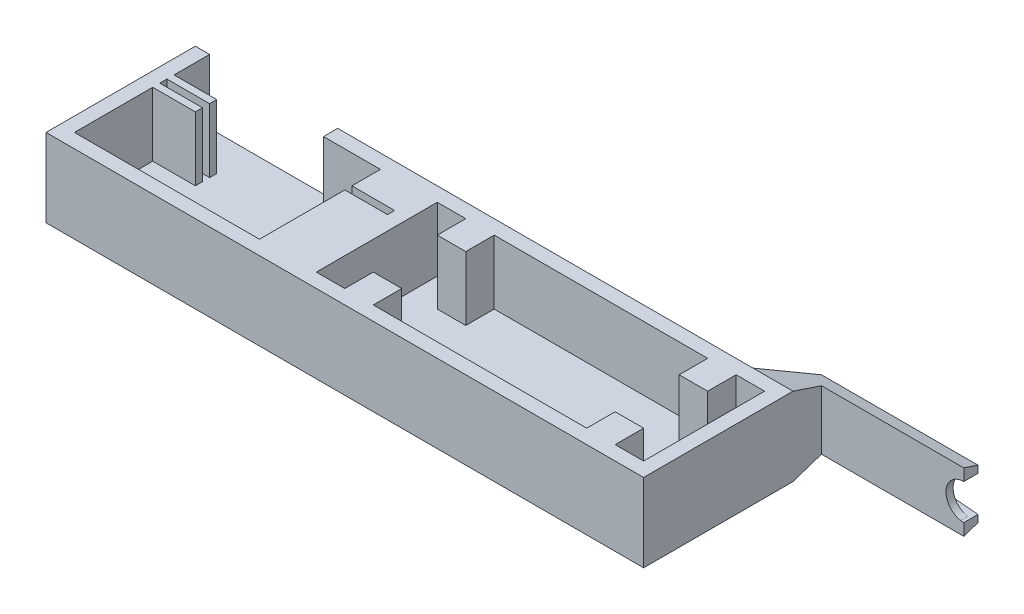
SolidWorks part; units mm, degrees
ref_plane "Front Plane" through (0, 0, 0) normal (0, 0, 1) x (1, 0, 0)
ref_plane "Top Plane" through (0, 0, 0) normal (0, 1, 0) x (1, 0, 0)
ref_plane "Right Plane" through (0, 0, 0) normal (1, 0, 0) x (0, 0, -1)
sketch "Sketch1" plane through (0, 0, 0) normal (0, 1, 0) x (1, 0, 0)
  line L0 (0, 0) -> (40, 0) construction
  line L1 (0, 0) -> (-40, 0) construction
  line L2 (40, -8.5) -> (40, 8.5)
  line L3 (40, 8.5) -> (-40, 8.5)
  line L4 (-40, 8.5) -> (-40, -8.5)
  line L5 (-40, -8.5) -> (40, -8.5)
  line L6 (40, 8.5) -> (40, 10.5) construction
  line L7 (40, 10.5) -> (42, 10.5) construction
  line L8 (-40, -8.5) -> (-40, -10.5) construction
  line L9 (-40, -10.5) -> (-42, -10.5) construction
  line L10 (-40, 0) -> (-34, 0) construction
  line L11 (-42, -10.5) -> (42, -10.5)
  line L12 (-42, -10.5) -> (-42, 10.5)
  line L13 (-42, 10.5) -> (42, 10.5)
  line L14 (42, -10.5) -> (42, 10.5)
  line L15 (-34, 0) -> (-14, 0) construction
  line L16 (-34, -8.5) -> (-34, 3.5)
  line L17 (-34, 3.5) -> (-40, 3.5)
  line L18 (-40, 3.5) -> (-40, 4.4487)
  line L19 (-34, 4.5) -> (-40, 4.5)
  line L20 (-34, 4.5) -> (-34, 8.5)
  line L21 (-14, 3.5) -> (-14, -8.5)
  line L22 (-14, 3.5) -> (-8, 3.5)
  line L23 (-8, 3.5) -> (-8, 4.5)
  line L24 (-8, 4.5) -> (-14, 4.5)
  line L25 (-14, 4.5) -> (-14, 8.5)
  line L26 (-8, 3.5) -> (-6, 3.5) construction
  line L27 (-6, 8.5) -> (-6, -8.5)
  line L28 (62, 14.5) -> (42, 14.5)
  line L29 (42, 14.5) -> (42, 10.5)
  line L30 (62, 16.5) -> (40, 16.5)
  line L31 (40, 16.5) -> (36.3801, 10.5)
  line L32 (62, 14.5) -> (62, 16.5)
  line L33 (40, 10.5) -> (36.3801, 10.5) construction
  point P7 (40, 0)
extrude "Boss-Extrude1" add sketch "Sketch1" along normal blind 2 contours L31 L13 L29 L28 L32 L30 | L3 L27 L5 L2 | L27 L3 L25 L24 L23 L22 L21 L5 | L19 L20 L3 L4 | L24 L25 L3 L20 L19 L4 L17 L16 L5 L21 L22 L23 | L16 L17 L4 L5 | L11 L14 L13 L12 L5 L4 L3 L2 region at (17, 0, 0) region at (-9.9538, 0, 0.1846) region at (-24, 0, -0.1364) region at (-37, 0, 2.5) region at (-37, 0, -6.5) region at (-41.1341, 0, 0) region at (47.6185, 0, -14.5999)
extrude "Boss-Extrude2" add sketch "Sketch1<4>" along normal blind 11 contours L31 L13 L29 L28 L32 L30 | L11 L14 L13 L12 L5 L4 L3 L2 | L27 L3 L25 L24 L23 L22 L21 L5 | L16 L17 L4 L5 | L19 L20 L3 L4 region at (-9.9538, 0, 0.1846) region at (-37, 0, 2.5) region at (-37, 0, -6.5) region at (-41.1341, 0, 0) region at (47.6185, 0, -14.5999)
sketch "Sketch1<4>" plane through (0, 0, 0) normal (0, 1, 0) x (1, 0, 0) same geometry as "Sketch1"
sketch "Sketch2" plane through (0, 11, 0) normal (0, 1, 0) x (1, 0, 0)
  line L1 (-40, 5.5) -> (-34, 5.5)
  line L2 (-34, 4.5) -> (-34, 8.5) construction
  line L3 (-34, 5.5) -> (-34, 8.5)
  line L4 (-34, 8.5) -> (-40, 8.5)
  line L5 (-40, 8.5) -> (-40, 5.5)
  line L6 (-40, 2.5) -> (-34, 2.5)
  line L7 (-34, -8.5) -> (-34, 3.5) construction
  line L8 (-34, 2.5) -> (-34, -8.5)
  line L9 (-34, -8.5) -> (-40, -8.5)
  line L10 (-40, -8.5) -> (-40, 2.5)
extrude "Cut-Extrude1" cut sketch "Sketch2" against normal blind 9
sketch "Sketch3" plane through (0, 0, -10.5) normal (0, 0, -1) x (-1, 0, 0)
  line L0 (42, 9) -> (40, 9) construction
  line L1 (42, 11) -> (42, 0) construction
  line L2 (40, 2) -> (22, 2)
  line L4 (40, 0) -> (40, 2) construction
  line L5 (42, 0) -> (-36.3801, 0) construction
  line L6 (22, 2) -> (22, 11)
  line L7 (42, 11) -> (-36.3801, 11) construction
  line L8 (22, 11) -> (40, 11)
  line L9 (40, 11) -> (40, 2)
extrude "Cut-Extrude2" cut sketch "Sketch3" against normal blind 2
sketch "Sketch4" plane through (0, 2, 0) normal (0, 1, 0) x (1, 0, 0)
  line L0 (-6, 8.5) -> (-2, 8.5) construction
  line L1 (40, 8.5) -> (-6, 8.5) construction
  line L2 (-2, 8.5) -> (-2, 4.5)
  line L3 (-2, 4.5) -> (2, 4.5)
  line L4 (2, 4.5) -> (2, 8.5)
  line L5 (-6, 8.5) -> (40, 8.5) construction
  line L6 (2, 8.5) -> (-2, 8.5)
  line L7 (-2, -8.5) -> (-2, -4.5)
  line L8 (40, -8.5) -> (-6, -8.5) construction
  line L9 (-2, -4.5) -> (2, -4.5)
  line L10 (2, -4.5) -> (2, -8.5)
  line L11 (-6, -8.5) -> (40, -8.5) construction
  line L12 (2, -8.5) -> (-2, -8.5)
  line L13 (40, 8.5) -> (36, 8.5) construction
  line L14 (36, 8.5) -> (36, 4.5)
  line L15 (36, 4.5) -> (32, 4.5)
  line L16 (32, 4.5) -> (32, 8.5)
  line L17 (32, 8.5) -> (36, 8.5)
  line L18 (36, -8.5) -> (36, -4.5)
  line L19 (36, -4.5) -> (32, -4.5)
  line L20 (32, -4.5) -> (32, -8.5)
  line L21 (32, -8.5) -> (36, -8.5)
extrude "Boss-Extrude3" add sketch "Sketch4" along normal blind 9 contours L6 L2 L3 L4 | L12 L7 L9 L10 | L21 L18 L19 L20 | L17 L14 L15 L16
sketch "Sketch6" plane through (0, 0, -16.5) normal (0, 0, -1) x (-1, 0, 0)
  line L0 (-62, 11) -> (-62, 5.5) construction
  line L1 (-62, 5.5) -> (-55.5, 5.5) construction
  line L2 (-62, 11) -> (-62, 0) construction
  line L3 (-62, 5.5) -> (-50.5, 5.5) construction
  line L4 (-62, 3) -> (-50.5, 4)
  line L5 (-50.5, 7) -> (-62, 8)
  line L6 (-50.5, 5.5) -> (-53, 5.5) construction
  circle A0 centre (-50.5, 5.5) radius 0.5
  circle A1 centre (-50.5, 5.5) radius 1.5
  circle A2 centre (-62, 5.5) radius 2.5
  circle A3 centre (-53, 5.5) radius 0.5
  circle A4 centre (-55.5, 5.5) radius 0.5
  line M5 (-62, 11) -> (-62, 0)
extrude "Cut-Extrude3" cut sketch "Sketch6" against normal blind 1 contours A2 L4 A1 L5 A4 A3 | A1 A0 region at (56.1616, 5.5, -16.5) region at (51.9576, 5.5, -16.5)
extrude "Cut-Extrude4" cut sketch "Sketch6<3>" against normal blind 2 contours L4 A2 L5 M5 region at (60.9385, 5.5, -16.5)
sketch "Sketch6<3>" plane through (0, 0, -16.5) normal (0, 0, -1) x (-1, 0, 0) same geometry as "Sketch6"
sketch "Sketch7" plane through (42, 0, 0) normal (1, 0, 0) x (0, 0, -1)
  line L0 (-10.5, 11) -> (10.5, 11) construction
  line L1 (14.5, 11) -> (-10.5, 11) construction
  line L2 (16.5, 8) -> (16.5, 9) construction
  line L3 (16.5, 11) -> (16.5, 8) construction
  line L4 (10.5, 0) -> (16.5, 2)
  line L5 (10.5, 11) -> (10.5, 0) construction
  line L6 (16.5, 2) -> (16.5, 0)
  line L7 (16.5, 3) -> (16.5, 0) construction
  line L8 (16.5, 2) -> (16.5, 3) construction
  line L9 (16.5, 0) -> (10.5, 0)
  line L10 (10.5, 11) -> (16.5, 9)
  line L11 (16.5, 9) -> (16.5, 11)
  line L12 (16.5, 11) -> (10.5, 11)
extrude "Cut-Extrude5" cut sketch "Sketch7" against normal blind 13 and the other way blind 34 contours L12 L10 L11 | L9 L4 L6
